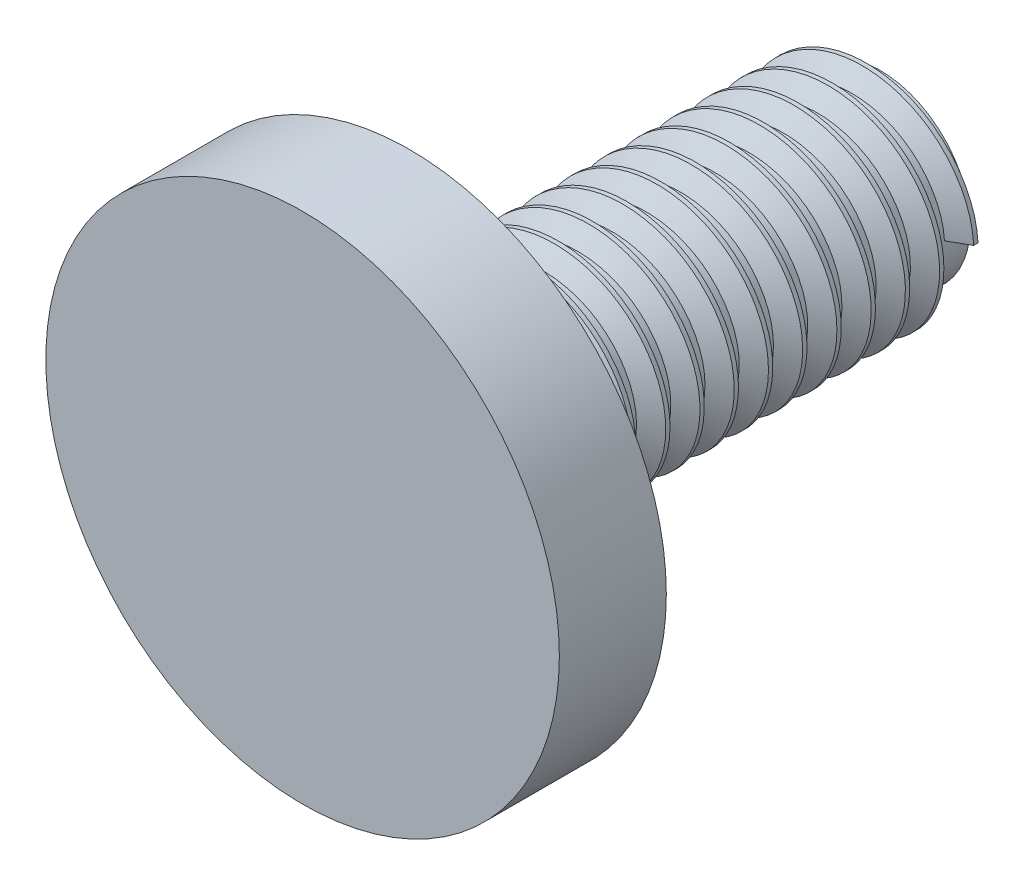
SolidWorks part; units mm, degrees
material "黄铜"
ref_plane "前视基准面" through (0, 0, 0) normal (0, 0, 1) x (1, 0, 0)
ref_plane "上视基准面" through (0, 0, 0) normal (0, 1, 0) x (1, 0, 0)
ref_plane "右视基准面" through (0, 0, 0) normal (1, 0, 0) x (0, 0, -1)
sketch "草图1" plane through (0, 0, 0) normal (0, 0, 1) x (1, 0, 0)
  circle A0 centre (0, 0) radius 6
extrude "凸台-拉伸1" add sketch "草图1" along normal blind 2.5
sketch "草图2" plane through (0, 0, 0) normal (0, 0, 1) x (1, 0, 0)
  circle A0 centre (0, 0) radius 2.1
extrude "凸台-拉伸2" add sketch "草图2" against normal blind 11 from surface starting at face at (6, 0, 0)
thread "螺纹线2" pitch 0.8 method extrude trim with end face yes profile "螺纹线轮廓3" start angle 0, offset 0, length 11, pitch 0.8, diameter 4.2
ref_plane "基准面3" through (2.1, 0, -11) normal (0, -1, 0) x (1, 0, 0)
sketch "螺纹线轮廓3" plane through (2.1, 0, -11) normal (0, -1, 0) x (1, 0, 0)
  line L0 (0, 0) -> (0, 0.8) construction
  line L1 (0, 0) -> (0.433, 0.25)
  line L2 (0.433, 0.25) -> (0.433, 0.35)
  line L3 (0.433, 0.35) -> (0, 0.6)
  line L4 (0.433, 0.3) -> (0, 0.3) construction
  line L11 (0, 0) -> (0, 0.6)
  point P2 (0, 0)
  dimension "Pitch" = 0.8
  dimension "Profile_Angle" = 60
  dimension "Profile_Land" = 0.1
  dimension "Profile_Height" = 0.433
